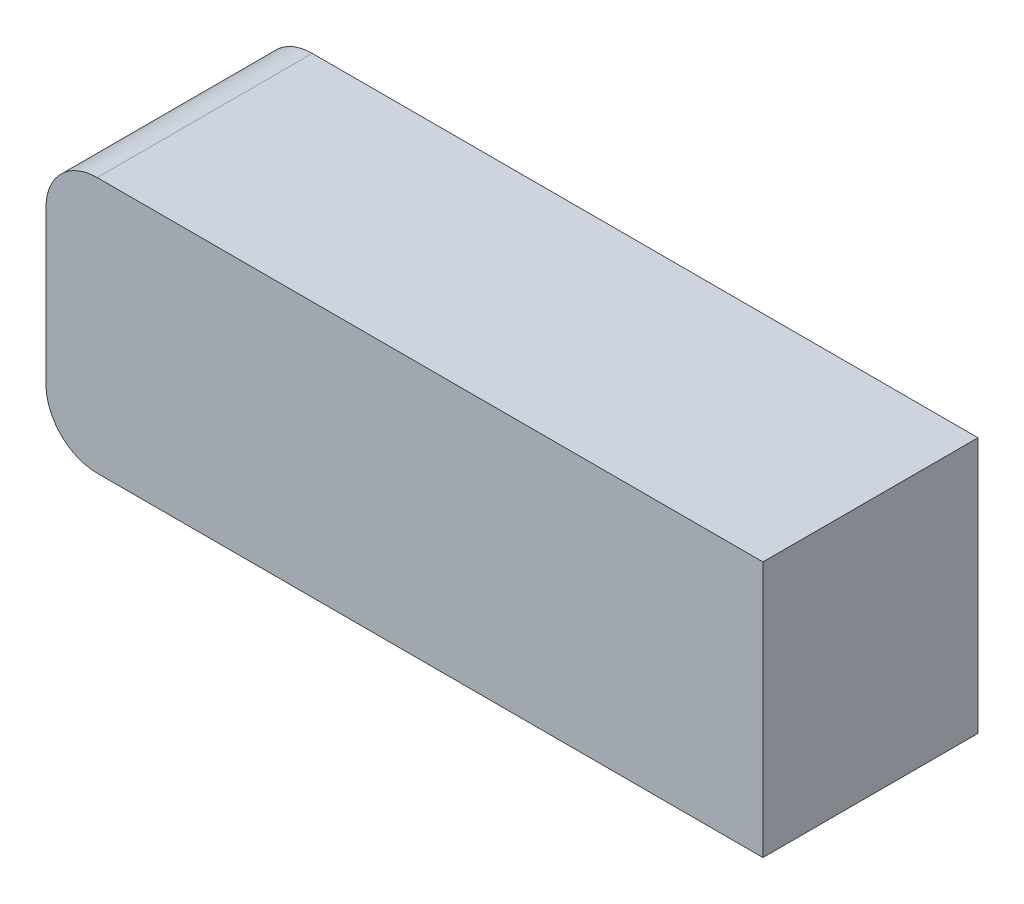
SolidWorks part; units mm, degrees
ref_plane "Alzado" through (0, 0, 0) normal (0, 0, 1) x (1, 0, 0)
ref_plane "Planta" through (0, 0, 0) normal (0, 1, 0) x (1, 0, 0)
ref_plane "Vista lateral" through (0, 0, 0) normal (1, 0, 0) x (0, 0, -1)
sketch "Croquis2" plane through (0, 0, 0) normal (0, 1, 0) x (1, 0, 0)
  line L1 (70, -21) -> (-70, -21)
  line L2 (70, -21) -> (70, 21)
  line L3 (70, 21) -> (-70, 21)
  line L4 (-70, -21) -> (-70, 21)
  line L5 (70, -21) -> (-70, 21) construction
  line L6 (70, 21) -> (-70, -21) construction
  point P0 (0, 0)
  dimension "D1" = 140
  dimension "D2" = 42
extrude "Saliente-Extruir1" add sketch "Croquis2" along normal mid plane 50
fillet "Redondeo1" radius 10 2 edges at (-70, -25, 0) (-70, 25, 0)
